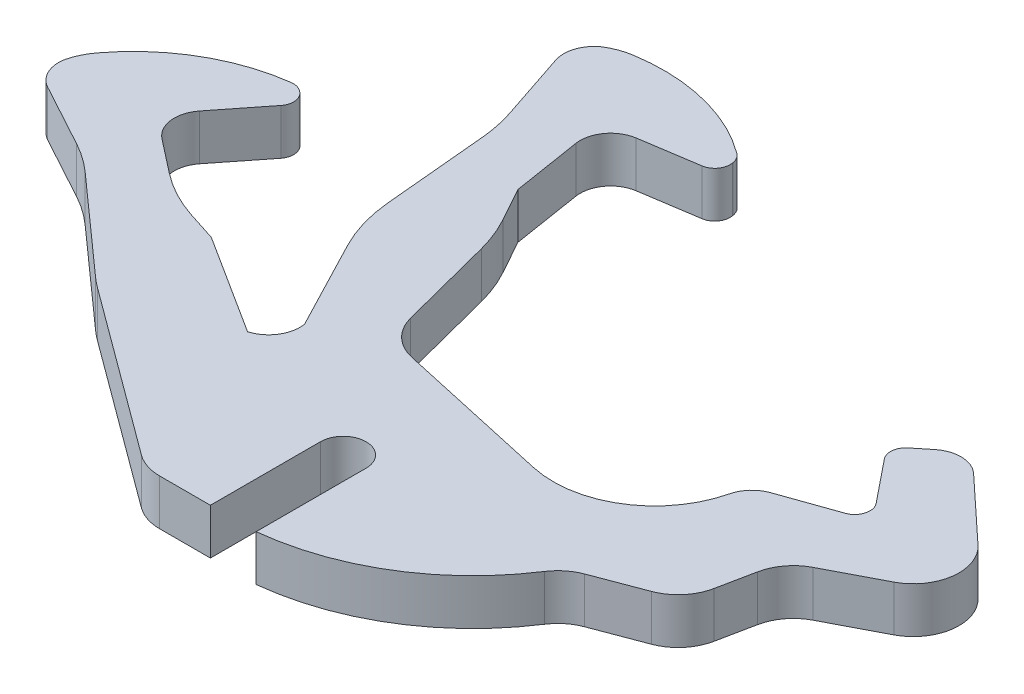
SolidWorks part; units mm, degrees
ref_plane "Front Plane" through (0, 0, 0) normal (0, 0, 1) x (1, 0, 0)
ref_plane "Top Plane" through (0, 0, 0) normal (0, 1, 0) x (1, 0, 0)
ref_plane "Right Plane" through (0, 0, 0) normal (1, 0, 0) x (0, 0, -1)
sketch "Sketch1" plane through (0, 0, 0) normal (0, 1, 0) x (1, 0, 0)
  line L0 (0, 0) -> (0, 7.21)
  line L1 (3, 7.21) -> (3, 0)
  line L2 (22, 15.56) -> (20.9, 10.15)
  line L3 (-3.6, 15.4) -> (-6, 24.68)
  line L4 (-6, 24.68) -> (-7.8452, 28)
  line L5 (22, 15.56) -> (30.53, 20)
  line L6 (30.53, 20) -> (21.94, 28)
  line L7 (21.94, 28) -> (18.8345, 25.4948)
  line L8 (-2.3872, 36.974) -> (-2.1522, 35.5299)
  line L9 (-2.1522, 35.5299) -> (-8.88, 34.5)
  line L10 (8.4678, 12.7282) -> (-3.6, 15.4)
  line L11 (20.9, 10.15) -> (15.2, 8)
  line L12 (18.8345, 25.4948) -> (22.6017, 20.8249)
  line L13 (22.6017, 20.8249) -> (16.53, 18.68)
  line L14 (-8.88, 34.5) -> (-7.8452, 28)
  line L15 (-12.7223, 39.1996) -> (-14.4122, 37.9686)
  line L16 (-14.4122, 37.9686) -> (-12.0833, 30.9818)
  line L17 (-12.0833, 30.9818) -> (-11.1606, 20.989)
  line L18 (-11.1606, 20.989) -> (-7.1877, 13.3565)
  line L19 (-23.8817, 15.5785) -> (-16.3919, 8.8995)
  line L20 (-30.35, 19.1) -> (-23.8817, 15.5785)
  line L21 (-29.9535, 21.1528) -> (-30.35, 19.1)
  line L22 (-20.9172, 26.6919) -> (-19.7605, 25.7959)
  line L23 (-19.7605, 25.7959) -> (-23.9785, 20.4544)
  line L24 (-23.9785, 20.4544) -> (-18.7887, 16.4063)
  line L25 (-15.175, 15.2366) -> (-18.7887, 16.4063)
  line L26 (-8.634, 11.0696) -> (-15.175, 15.2366)
  line L27 (-16.3919, 8.8995) -> (-4.31, 0)
  line L28 (-4.31, 0) -> (0, 0)
  arc A0 (0, 7.21) -> (3, 7.21) centre (1.5, 7.21) cw
  arc A1 (3, 0) -> (15.2, 8) centre (1.2788, 15.9274) ccw
  arc A2 (8.4678, 12.7282) -> (16.53, 18.68) centre (9.9047, 19.2182) ccw
  arc A3 (-12.7223, 39.1996) -> (-2.3872, 36.974) centre (-9.8148, 27.5915) cw
  arc A4 (-7.1877, 13.3565) -> (-8.634, 11.0696) centre (-9.205, 13.0315) cw
  arc A5 (-29.9535, 21.1528) -> (-20.9172, 26.6919) centre (-19.8282, 14.7748) cw
  point P7 (30.53, 20)
  point P8 (-11.42, 39.45)
  point P31 (-30.35, 19.1)
  point P39 (-6, 24.68)
  dimension "D2" = 1.5
  dimension "D26" = 16.0201
  dimension "D27" = 6.6472
  dimension "D28" = 11.9667
  dimension "D45" = 2.0433
  dimension "D1" = 12.2
  dimension "D3" = 7.21
  dimension "D4" = 8
  dimension "D5" = 20
  dimension "D6" = 27.53
  dimension "D7" = 8.59
  dimension "D8" = 28
  dimension "D9" = 3.99
  dimension "D10" = 13.53
  dimension "6" = 6
  dimension "D11" = 18.68
  dimension "D12" = 19
  dimension "D13" = 15.56
  dimension "D14" = 17.9
  dimension "D15" = 10.15
  dimension "D16" = 12.36
  dimension "D17" = 15.4
  dimension "D18" = 3.6
  dimension "D19" = 24.68
  dimension "D20" = 6
  dimension "D21" = 39.45
  dimension "D22" = 11.42
  dimension "D23" = 8.88
  dimension "D24" = 34.5
  dimension "D25" = 12.26
  dimension "D29" = 18.8345
  dimension "D30" = 13.3565
  dimension "D31" = 2.1522
  dimension "D32" = 2.3872
  dimension "D33" = 7.1877
  dimension "D34" = 7.8452
  dimension "D35" = 9.8148
  dimension "D36" = 11.1606
  dimension "D37" = 12.0833
  dimension "D38" = 12.7223
  dimension "D39" = 30.35
  dimension "D40" = 30.9818
  dimension "D41" = 35.5299
  dimension "D42" = 37.9686
  dimension "D43" = 19.1
  dimension "D44" = 4.31
  dimension "D46" = 8.634
  dimension "D47" = 15.175
  dimension "D48" = 18.7887
  dimension "D49" = 16.3919
  dimension "D50" = 19.7605
  dimension "D51" = 19.8282
  dimension "D52" = 20.9172
  dimension "D53" = 23.9785
  dimension "D54" = 23.8817
extrude "Boss-Extrude1" add sketch "Sketch1" along normal blind 3
fillet "Fillet1" radius 10 6 edges at (-12.0833, 1.5, -30.9818) (-11.1606, 1.5, -20.989) (-6, 1.5, -24.68) (-23.8817, 1.5, -15.5785) (-16.3919, 1.5, -8.8995) (-18.7887, 1.5, -16.4063)
fillet "Fillet2" radius 2 2 edges at (-14.4122, 1.5, -37.9686) (-30.35, 1.5, -19.1)
fillet "Fillet3" radius 4 2 edges at (-12.7223, 1.5, -39.1996) (-29.9535, 1.5, -21.1528)
fillet "Fillet4" radius 1 4 edges at (-2.3872, 1.5, -36.974) (-2.1522, 1.5, -35.5299) (-20.9172, 1.5, -26.6919) (-19.7605, 1.5, -25.7959)
fillet "Fillet5" radius 2 2 edges at (-8.88, 1.5, -34.5) (-23.9785, 1.5, -20.4544)
fillet "Fillet6" radius 3 6 edges at (-4.31, 1.5, 0) (15.2, 1.5, -8) (20.9, 1.5, -10.15) (22, 1.5, -15.56) (30.53, 1.5, -20) (-3.6, 1.5, -15.4)
fillet "Fillet7" radius 2 2 edges at (21.94, 1.5, -28) (16.53, 1.5, -18.68)
fillet "Fillet8" radius 1 2 edges at (18.8345, 1.5, -25.4948) (22.6017, 1.5, -20.8249)
